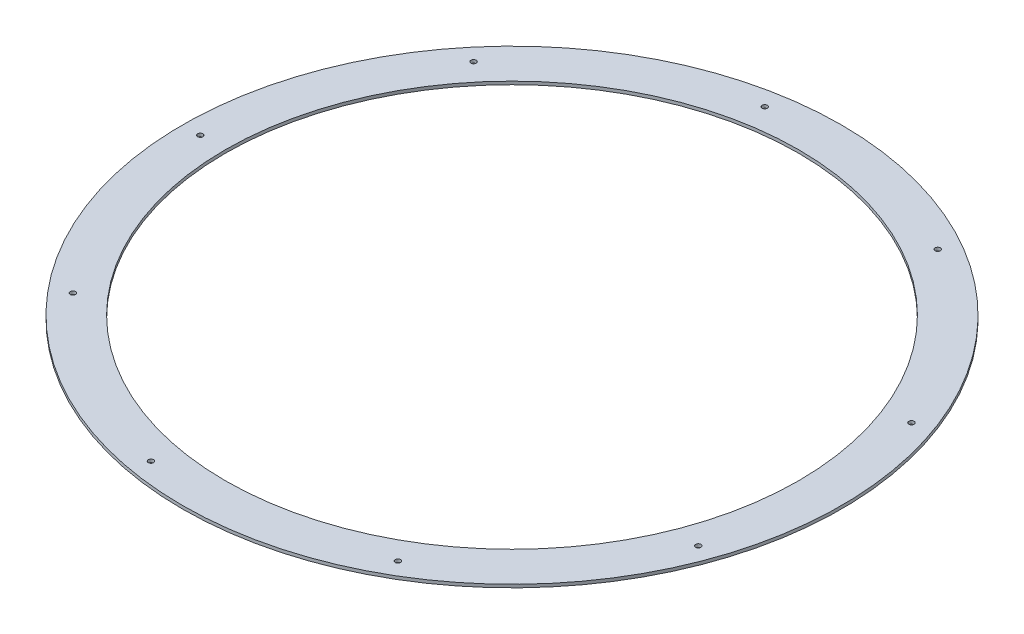
SolidWorks part; units mm, degrees
ref_plane "Front Plane" through (0, 0, 0) normal (0, 0, 1) x (1, 0, 0)
ref_plane "Top Plane" through (0, 0, 0) normal (0, 1, 0) x (1, 0, 0)
ref_plane "Right Plane" through (0, 0, 0) normal (1, 0, 0) x (0, 0, -1)
sketch "Sketch1" plane through (0, 0, 0) normal (0, 1, 0) x (1, 0, 0)
  circle A0 centre (0, 0) radius 318.262
  circle A1 centre (0, 0) radius 276.86
  dimension "D1" = 636.524
  dimension "D2" = 41.402
extrude "Boss-Extrude1" add sketch "Sketch1" along normal blind 2.9972
ref_axis "Axis1" through (0, 3.3337, 0) along (0, -1, 0)
sketch "Sketch2" plane through (0, 2.9972, 0) normal (0, 1, 0) x (1, 0, 0)
  line L0 (0, 0) -> (-300.99, 0) construction
  circle A0 centre (-300.99, 0) radius 2.5527
  dimension "D2" = 5.1054
  dimension "D1" = 300.99
extrude "Cut-Extrude1" cut sketch "Sketch2" against normal through all
pattern_circular "CirPattern1" count 9 over 360 about axis through (0, 3.3337, 0) along (0, -1, 0) of "Cut-Extrude1"
